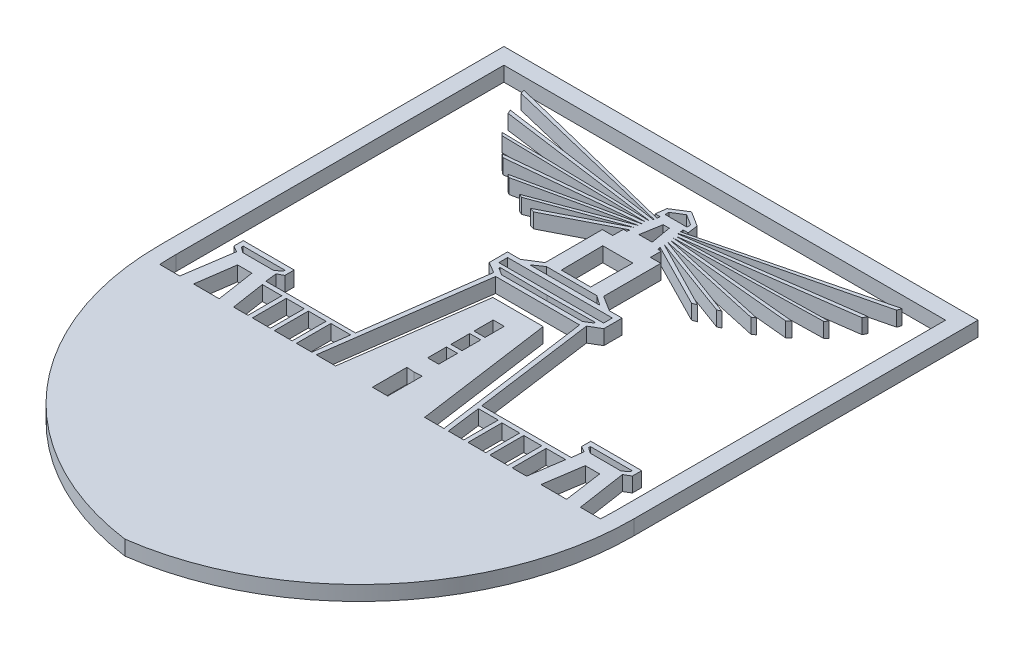
SolidWorks part; units mm, degrees
material "Acrylic (Medium-high impact)"
ref_plane "Front Plane" through (0, 0, 0) normal (0, 0, 1) x (1, 0, 0)
ref_plane "Top Plane" through (0, 0, 0) normal (0, 1, 0) x (1, 0, 0)
ref_plane "Right Plane" through (0, 0, 0) normal (1, 0, 0) x (0, 0, -1)
sketch "Sketch1" plane through (0, 0, 0) normal (0, 1, 0) x (1, 0, 0)
  line L0 (0, 0) -> (5, 0) construction
  line L1 (338.282, 207.287) -> (338.282, 90.5991)
  line L2 (338.282, 207.287) -> (418.6487, 207.287)
  line L3 (418.6487, 207.287) -> (418.6487, 205.1656) construction
  line L4 (343.782, 201.787) -> (418.6487, 201.787)
  line L5 (343.782, 201.787) -> (343.782, 90.5991)
  line L6 (343.9648, 84.9427) -> (350.7389, 84.9427)
  line L7 (350.7389, 84.9427) -> (353.2346, 101.6759)
  line L8 (353.2346, 101.6759) -> (351.1115, 102.9309)
  line L9 (351.1115, 102.9309) -> (351.1115, 106.1012)
  line L10 (351.1115, 106.1012) -> (368.3755, 106.1012)
  line L11 (368.3755, 106.1012) -> (368.3755, 102.9309)
  line L12 (368.3755, 102.9309) -> (366.4294, 101.8951)
  line L13 (366.4294, 101.8951) -> (366.8689, 98.0028)
  line L14 (366.8689, 98.0028) -> (397.265, 98.0028)
  line L15 (397.265, 98.0028) -> (402.9132, 139.1779)
  line L16 (402.9132, 139.1779) -> (399.2205, 141.3608)
  line L17 (399.2205, 141.3608) -> (399.2205, 147.5615)
  line L18 (399.2205, 147.5615) -> (403.5436, 147.5615)
  line L19 (403.5436, 147.5615) -> (408.7386, 150.824)
  line L20 (408.7386, 150.824) -> (408.7386, 170.1989)
  line L21 (408.7386, 170.1989) -> (412.2526, 170.1989)
  line L22 (412.2526, 170.1989) -> (412.2526, 173.8284)
  line L23 (412.2526, 173.8284) -> (413.3988, 173.8284)
  line L24 (413.3988, 173.8284) -> (414.7661, 183.7962)
  line L25 (414.7661, 183.7962) -> (413.0651, 183.7962)
  line L26 (413.0651, 183.7962) -> (413.5499, 187.3303)
  line L27 (413.5499, 187.3303) -> (418.6487, 190.5324)
  line L28 (350.7389, 84.9427) -> (486.5585, 84.9427)
  line L29 (355.4177, 84.9427) -> (357.2644, 98.0028)
  line L30 (357.2644, 98.0028) -> (362.135, 98.0028)
  line L31 (362.135, 98.0028) -> (364.0997, 84.9427)
  line L32 (357.2765, 84.9427) -> (358.6439, 96.4394)
  line L33 (358.6439, 96.4394) -> (360.8995, 96.4394)
  line L34 (360.8995, 96.4394) -> (362.5434, 84.9427)
  line L35 (352.719, 104.4668) -> (366.8689, 104.4668)
  line L36 (366.8689, 104.4668) -> (366.8689, 103.849)
  line L37 (366.8689, 103.849) -> (364.951, 102.4899)
  line L38 (364.951, 102.4899) -> (354.5312, 102.4899)
  line L39 (354.5312, 102.4899) -> (352.719, 103.849)
  line L40 (352.719, 103.849) -> (352.719, 104.4668)
  line L41 (403.5578, 84.9427) -> (410.1037, 131.7143)
  line L42 (410.1037, 131.7143) -> (427.1937, 131.7143)
  line L43 (400.8893, 142.966) -> (436.408, 142.966)
  line L44 (418.6487, 142.966) -> (418.6487, 145.9394)
  line L45 (436.408, 145.9394) -> (400.8893, 145.9394)
  line L46 (400.8893, 145.9394) -> (400.8893, 142.966)
  line L47 (402.5078, 141.7616) -> (402.5078, 141.3608)
  line L48 (402.5078, 141.3608) -> (404.9542, 139.842)
  line L49 (404.9542, 139.842) -> (432.3431, 139.842)
  line L50 (418.6487, 139.842) -> (418.6487, 141.5616)
  line L51 (418.6487, 141.5616) -> (402.5078, 141.7616)
  line L52 (406.8086, 147.5615) -> (410.1037, 149.8728)
  line L53 (410.1037, 149.8728) -> (427.1937, 149.8728)
  line L54 (406.8086, 147.5615) -> (430.4887, 147.5615)
  line L55 (414.6308, 182.8096) -> (354.5312, 197.8348)
  line L56 (354.5312, 197.8348) -> (354.9929, 196.4245)
  line L57 (354.9929, 196.4245) -> (414.5137, 181.9557)
  line L58 (414.4848, 181.745) -> (358.0193, 189.685)
  line L59 (358.0193, 189.685) -> (358.6488, 188.3516)
  line L60 (358.6488, 188.3516) -> (414.343, 180.7117)
  line L61 (414.343, 180.7117) -> (363.2021, 181.745)
  line L62 (363.2021, 181.745) -> (364.1351, 180.7734)
  line L63 (364.1351, 180.7734) -> (414.2127, 179.7616)
  line L64 (422.3648, 185.2721) -> (414.9326, 185.2721)
  line L65 (414.9326, 185.2721) -> (414.9326, 186.5349)
  line L66 (414.9326, 186.5349) -> (418.6487, 188.849)
  line L67 (373.8379, 84.9427) -> (373.8379, 96.4394)
  line L68 (373.8379, 96.4394) -> (367.2313, 96.4394)
  line L69 (367.2313, 96.4394) -> (368.987, 84.9427)
  line L70 (375.3556, 96.4394) -> (375.3556, 84.9427)
  line L71 (375.3556, 84.9427) -> (381.4265, 84.9427)
  line L72 (381.4265, 84.9427) -> (381.4265, 96.4394)
  line L73 (381.4265, 96.4394) -> (375.3556, 96.4394)
  line L74 (382.8287, 84.9427) -> (382.8287, 96.4463)
  line L75 (382.8287, 96.4463) -> (388.8336, 96.4463)
  line L76 (388.8336, 96.4463) -> (388.8336, 84.9427)
  line L77 (390.2871, 96.6243) -> (390.2871, 84.9427)
  line L78 (390.2871, 96.6243) -> (396.9907, 96.6243)
  line L79 (396.9907, 96.6243) -> (395.491, 84.9427)
  line L80 (397.0048, 84.9427) -> (404.4186, 138.3529)
  line L81 (404.4186, 138.3529) -> (432.8787, 138.3529)
  line L82 (419.6894, 181.9557) -> (417.6079, 181.9557)
  line L83 (417.6079, 181.9557) -> (416.4096, 174.941)
  line L84 (416.4096, 174.941) -> (420.8877, 174.941)
  line L85 (418.8634, 180.9228) -> (418.434, 180.9228)
  line L86 (418.434, 180.9228) -> (417.8251, 176.113)
  line L87 (417.8251, 176.113) -> (419.4722, 176.113)
  line L88 (412.2526, 151.358) -> (412.2526, 167.1023)
  line L89 (412.2526, 167.1023) -> (425.0447, 167.1023)
  line L90 (423.7475, 165.5348) -> (413.5499, 165.5348)
  line L91 (413.5499, 165.5348) -> (413.6837, 151.358)
  line L92 (413.6837, 151.358) -> (423.6137, 151.358)
  line L93 (418.434, 130.1574) -> (411.6143, 130.1574)
  line L94 (411.6143, 130.1574) -> (404.9692, 84.9427)
  line L95 (414.2127, 179.7616) -> (369.5177, 175.4706)
  line L96 (369.5177, 175.4706) -> (370.7239, 174.4757)
  line L97 (370.7239, 174.4757) -> (413.9507, 178.6258)
  line L98 (413.9507, 178.6258) -> (376.4718, 170.4145)
  line L99 (376.4718, 170.4145) -> (377.6526, 169.6582)
  line L100 (377.6526, 169.6582) -> (413.9166, 177.6033)
  line L101 (413.9166, 177.6033) -> (384.3715, 166.5403)
  line L102 (384.3715, 166.5403) -> (385.5687, 165.9954)
  line L103 (385.5687, 165.9954) -> (413.7408, 176.3215)
  line L104 (413.7408, 176.3215) -> (390.2871, 164.2335)
  line L105 (390.2871, 164.2335) -> (391.8652, 163.7288)
  line L106 (391.8652, 163.7288) -> (413.529, 174.7775)
  line L107 (414.4848, 85.1259) -> (414.4848, 98.0028)
  line L108 (414.4848, 98.0028) -> (422.8126, 98.0028)
  line L109 (416.0563, 84.9427) -> (416.0563, 96.6243)
  line L110 (416.0563, 96.6243) -> (418.6487, 96.4463)
  line L111 (420.5185, 102.9309) -> (416.7789, 102.9309)
  line L112 (416.7789, 102.9309) -> (416.7789, 109.3146)
  line L113 (416.7789, 109.3146) -> (420.5185, 109.3146)
  line L114 (419.3869, 108.1591) -> (417.9105, 108.1591)
  line L115 (417.9105, 108.1591) -> (417.9105, 103.9613)
  line L116 (417.9105, 103.9613) -> (419.3869, 103.9613)
  line L117 (420.5185, 125.164) -> (416.7789, 125.164)
  line L118 (416.7789, 125.164) -> (416.7789, 118.6557)
  line L119 (416.7789, 118.6557) -> (420.5185, 118.6557)
  line L120 (419.3869, 119.9212) -> (417.9105, 119.9212)
  line L121 (417.9105, 119.9212) -> (417.9105, 124.0341)
  line L122 (417.9105, 124.0341) -> (419.3869, 124.0341)
  line L123 (395.2823, 95.3731) -> (391.4774, 95.3731)
  line L124 (391.4774, 95.3731) -> (391.4774, 91.7404)
  line L125 (391.4774, 91.7404) -> (395.2823, 91.7404)
  line L126 (395.2823, 91.7404) -> (395.2823, 95.3731)
  line L127 (392.5991, 92.7292) -> (392.5991, 94.2466)
  line L128 (392.5991, 94.2466) -> (394.0882, 94.2466)
  line L129 (394.0882, 94.2466) -> (394.0882, 92.7434)
  line L130 (394.0882, 92.7434) -> (392.5991, 92.7292)
  line L131 (384.0554, 91.7404) -> (384.0554, 95.3731)
  line L132 (384.0554, 95.3731) -> (387.7088, 95.3731)
  line L133 (387.7088, 95.3731) -> (387.7088, 91.7404)
  line L134 (387.7088, 91.7404) -> (384.0554, 91.7404)
  line L135 (385.1139, 94.2466) -> (385.1139, 92.7292)
  line L136 (385.1139, 92.7292) -> (386.6701, 92.7292)
  line L137 (386.6701, 92.7292) -> (386.6701, 94.2466)
  line L138 (386.6701, 94.2466) -> (385.1139, 94.2466)
  line L139 (420.5185, 117.2088) -> (416.7789, 117.2088)
  line L140 (416.7789, 117.2088) -> (416.7789, 110.8551)
  line L141 (416.7789, 110.8551) -> (420.5185, 110.8551)
  line L142 (418.6487, 110.8551) -> (418.6487, 112.0248)
  line L143 (419.3869, 112.0248) -> (417.9105, 112.0248)
  line L144 (417.9105, 112.0248) -> (417.9105, 116.039)
  line L145 (417.9105, 116.039) -> (419.3869, 116.039)
  line L146 (376.4718, 91.6125) -> (380.3389, 91.6125)
  line L147 (380.3389, 91.6125) -> (380.3389, 95.3731)
  line L148 (380.3389, 95.3731) -> (376.4718, 95.3731)
  line L149 (376.4718, 95.3731) -> (376.4718, 91.6125)
  line L150 (377.6526, 94.2466) -> (377.6526, 92.7292)
  line L151 (377.6526, 92.7292) -> (379.2994, 92.7292)
  line L152 (379.2994, 92.7292) -> (379.2994, 94.2466)
  line L153 (379.2994, 94.2466) -> (377.6526, 94.2466)
  line L154 (379.2994, 94.2466) -> (379.0544, 93.6718)
  line L155 (368.987, 91.6125) -> (368.987, 95.3731)
  line L156 (368.987, 95.3731) -> (372.7392, 95.3731)
  line L157 (372.7392, 95.3731) -> (372.7392, 91.6125)
  line L158 (372.7392, 91.6125) -> (368.987, 91.6125)
  line L159 (370.043, 92.7292) -> (371.6081, 92.7292)
  line L160 (371.6081, 92.7292) -> (371.6081, 94.2484)
  line L161 (371.6081, 94.2484) -> (370.043, 94.2484)
  line L162 (370.043, 94.2484) -> (370.043, 92.7292)
  line L163 (467.2543, 94.2484) -> (467.2543, 92.7292)
  line L164 (465.6893, 94.2484) -> (467.2543, 94.2484)
  line L165 (465.6893, 92.7292) -> (465.6893, 94.2484)
  line L166 (467.2543, 92.7292) -> (465.6893, 92.7292)
  line L167 (464.5581, 91.6125) -> (468.3103, 91.6125)
  line L168 (464.5581, 95.3731) -> (464.5581, 91.6125)
  line L169 (468.3103, 95.3731) -> (464.5581, 95.3731)
  line L170 (468.3103, 91.6125) -> (468.3103, 95.3731)
  line L171 (457.9979, 94.2466) -> (458.243, 93.6718)
  line L172 (457.9979, 94.2466) -> (459.6448, 94.2466)
  line L173 (457.9979, 92.7292) -> (457.9979, 94.2466)
  line L174 (459.6448, 92.7292) -> (457.9979, 92.7292)
  line L175 (459.6448, 94.2466) -> (459.6448, 92.7292)
  line L176 (460.8255, 95.3731) -> (460.8255, 91.6125)
  line L177 (456.9585, 95.3731) -> (460.8255, 95.3731)
  line L178 (456.9585, 91.6125) -> (456.9585, 95.3731)
  line L179 (460.8255, 91.6125) -> (456.9585, 91.6125)
  line L180 (419.3869, 112.0248) -> (419.3869, 116.039)
  line L181 (420.5185, 117.2088) -> (420.5185, 110.8551)
  line L182 (450.6273, 94.2466) -> (452.1835, 94.2466)
  line L183 (450.6273, 92.7292) -> (450.6273, 94.2466)
  line L184 (452.1835, 92.7292) -> (450.6273, 92.7292)
  line L185 (452.1835, 94.2466) -> (452.1835, 92.7292)
  line L186 (449.5886, 91.7404) -> (453.242, 91.7404)
  line L187 (449.5886, 95.3731) -> (449.5886, 91.7404)
  line L188 (453.242, 95.3731) -> (449.5886, 95.3731)
  line L189 (453.242, 91.7404) -> (453.242, 95.3731)
  line L190 (443.2092, 92.7434) -> (444.6982, 92.7292)
  line L191 (443.2092, 94.2466) -> (443.2092, 92.7434)
  line L192 (444.6982, 94.2466) -> (443.2092, 94.2466)
  line L193 (444.6982, 92.7292) -> (444.6982, 94.2466)
  line L194 (442.0151, 91.7404) -> (442.0151, 95.3731)
  line L195 (445.82, 91.7404) -> (442.0151, 91.7404)
  line L196 (445.82, 95.3731) -> (445.82, 91.7404)
  line L197 (442.0151, 95.3731) -> (445.82, 95.3731)
  line L198 (419.3869, 119.9212) -> (419.3869, 124.0341)
  line L199 (420.5185, 125.164) -> (420.5185, 118.6557)
  line L200 (419.3869, 108.1591) -> (419.3869, 103.9613)
  line L201 (420.5185, 102.9309) -> (420.5185, 109.3146)
  line L202 (421.241, 96.6243) -> (418.6487, 96.4463)
  line L203 (421.241, 84.9427) -> (421.241, 96.6243)
  line L204 (422.8126, 85.1259) -> (422.8126, 98.0028)
  line L205 (445.4321, 163.7288) -> (423.7684, 174.7775)
  line L206 (447.0103, 164.2335) -> (445.4321, 163.7288)
  line L207 (423.5566, 176.3215) -> (447.0103, 164.2335)
  line L208 (451.7287, 165.9954) -> (423.5566, 176.3215)
  line L209 (452.9258, 166.5403) -> (451.7287, 165.9954)
  line L210 (423.3807, 177.6033) -> (452.9258, 166.5403)
  line L211 (459.6448, 169.6582) -> (423.3807, 177.6033)
  line L212 (460.8255, 170.4145) -> (459.6448, 169.6582)
  line L213 (423.3467, 178.6258) -> (460.8255, 170.4145)
  line L214 (466.5735, 174.4757) -> (423.3467, 178.6258)
  line L215 (467.7796, 175.4706) -> (466.5735, 174.4757)
  line L216 (423.0847, 179.7616) -> (467.7796, 175.4706)
  line L217 (425.683, 130.1574) -> (432.3282, 84.9427)
  line L218 (418.8634, 130.1574) -> (425.683, 130.1574)
  line L219 (423.7475, 165.5348) -> (423.6137, 151.358)
  line L220 (425.0447, 151.358) -> (425.0447, 167.1023)
  line L221 (418.8634, 180.9228) -> (419.4722, 176.113)
  line L222 (419.6894, 181.9557) -> (420.8877, 174.941)
  line L223 (440.2925, 84.9427) -> (432.8787, 138.3529)
  line L224 (440.3066, 96.6243) -> (441.8064, 84.9427)
  line L225 (447.0103, 96.6243) -> (440.3066, 96.6243)
  line L226 (447.0103, 96.6243) -> (447.0103, 84.9427)
  line L227 (448.4637, 96.4463) -> (448.4637, 84.9427)
  line L228 (454.4686, 96.4463) -> (448.4637, 96.4463)
  line L229 (454.4686, 84.9427) -> (454.4686, 96.4463)
  line L230 (455.8709, 96.4394) -> (461.9418, 96.4394)
  line L231 (455.8709, 84.9427) -> (455.8709, 96.4394)
  line L232 (461.9418, 84.9427) -> (455.8709, 84.9427)
  line L233 (461.9418, 96.4394) -> (461.9418, 84.9427)
  line L234 (470.066, 96.4394) -> (468.3103, 84.9427)
  line L235 (463.4595, 96.4394) -> (470.066, 96.4394)
  line L236 (463.4595, 84.9427) -> (463.4595, 96.4394)
  line L237 (422.3648, 186.5349) -> (418.6487, 188.849)
  line L238 (422.3648, 185.2721) -> (422.3648, 186.5349)
  line L239 (473.1622, 180.7734) -> (423.0847, 179.7616)
  line L240 (474.0953, 181.745) -> (473.1622, 180.7734)
  line L241 (422.9543, 180.7117) -> (474.0953, 181.745)
  line L242 (478.6486, 188.3516) -> (422.9543, 180.7117)
  line L243 (479.278, 189.685) -> (478.6486, 188.3516)
  line L244 (422.8126, 181.745) -> (479.278, 189.685)
  line L245 (482.3045, 196.4245) -> (422.7837, 181.9557)
  line L246 (482.7662, 197.8348) -> (482.3045, 196.4245)
  line L247 (422.6665, 182.8096) -> (482.7662, 197.8348)
  line L248 (430.4887, 147.5615) -> (427.1937, 149.8728)
  line L249 (418.6487, 141.5616) -> (434.7896, 141.7616)
  line L250 (434.7896, 141.3608) -> (432.3431, 139.842)
  line L251 (434.7896, 141.7616) -> (434.7896, 141.3608)
  line L252 (436.408, 145.9394) -> (436.408, 142.966)
  line L253 (433.7396, 84.9427) -> (427.1937, 131.7143)
  line L254 (484.5783, 103.849) -> (484.5783, 104.4668)
  line L255 (482.7662, 102.4899) -> (484.5783, 103.849)
  line L256 (472.3463, 102.4899) -> (482.7662, 102.4899)
  line L257 (470.4285, 103.849) -> (472.3463, 102.4899)
  line L258 (470.4285, 104.4668) -> (470.4285, 103.849)
  line L259 (484.5783, 104.4668) -> (470.4285, 104.4668)
  line L260 (476.3979, 96.4394) -> (474.7539, 84.9427)
  line L261 (478.6534, 96.4394) -> (476.3979, 96.4394)
  line L262 (480.0208, 84.9427) -> (478.6534, 96.4394)
  line L263 (475.1623, 98.0028) -> (473.1977, 84.9427)
  line L264 (480.0329, 98.0028) -> (475.1623, 98.0028)
  line L265 (481.8797, 84.9427) -> (480.0329, 98.0028)
  line L266 (423.7475, 187.3303) -> (418.6487, 190.5324)
  line L267 (424.2323, 183.7962) -> (423.7475, 187.3303)
  line L268 (422.5312, 183.7962) -> (424.2323, 183.7962)
  line L269 (423.8986, 173.8284) -> (422.5312, 183.7962)
  line L270 (425.0447, 173.8284) -> (423.8986, 173.8284)
  line L271 (425.0447, 170.1989) -> (425.0447, 173.8284)
  line L272 (428.5588, 170.1989) -> (425.0447, 170.1989)
  line L273 (428.5588, 150.824) -> (428.5588, 170.1989)
  line L274 (433.7538, 147.5615) -> (428.5588, 150.824)
  line L275 (438.0769, 147.5615) -> (433.7538, 147.5615)
  line L276 (438.0769, 141.3608) -> (438.0769, 147.5615)
  line L277 (434.3841, 139.1779) -> (438.0769, 141.3608)
  line L278 (440.0324, 98.0028) -> (434.3841, 139.1779)
  line L279 (470.4285, 98.0028) -> (440.0324, 98.0028)
  line L280 (470.8679, 101.8951) -> (470.4285, 98.0028)
  line L281 (468.9218, 102.9309) -> (470.8679, 101.8951)
  line L282 (468.9218, 106.1012) -> (468.9218, 102.9309)
  line L283 (486.1858, 106.1012) -> (468.9218, 106.1012)
  line L284 (486.1858, 102.9309) -> (486.1858, 106.1012)
  line L285 (484.0628, 101.6759) -> (486.1858, 102.9309)
  line L286 (486.5585, 84.9427) -> (484.0628, 101.6759)
  line L287 (493.3325, 84.9427) -> (486.5585, 84.9427)
  line L288 (493.5154, 201.787) -> (493.5154, 90.5991)
  line L289 (493.5154, 201.787) -> (418.6487, 201.787)
  line L290 (499.0154, 207.287) -> (418.6487, 207.287)
  line L291 (499.0154, 207.287) -> (499.0154, 90.5991)
  arc A0 (338.282, 90.5991) -> (418.6487, -1.6094) centre (431.3629, 90.5991) ccw
  arc A1 (343.782, 90.5991) -> (418.6487, 3.946) centre (431.3629, 90.5991) ccw
  arc A3 (493.5154, 90.5991) -> (418.6487, 3.946) centre (405.9345, 90.5991) cw
  arc A4 (499.0154, 90.5991) -> (418.6487, -1.6094) centre (405.9345, 90.5991) cw
  point P217 (418.6487, 116.039)
  point P220 (418.6487, 117.2088)
  point P237 (418.6487, 124.0341)
  point P238 (418.6487, 119.9212)
  point P239 (418.6487, 118.6557)
  point P240 (418.6487, 125.164)
  point P241 (418.6487, 103.9613)
  point P242 (418.6487, 108.1591)
  point P243 (418.6487, 109.3146)
  point P244 (418.6487, 102.9309)
  point P247 (418.6487, 98.0028)
  point P265 (418.6487, 151.358)
  point P266 (418.6487, 165.5348)
  point P267 (418.6487, 167.1023)
  point P269 (418.6487, 176.113)
  point P270 (418.6487, 180.9228)
  point P271 (418.6487, 174.941)
  point P272 (418.6487, 181.9557)
  point P273 (418.6487, 138.3529)
  point P292 (418.6487, 185.2721)
  point P303 (418.6487, 147.5615)
  point P304 (418.6487, 149.8728)
  point P310 (418.6487, 131.7143)
  point P326 (418.6487, 84.9427)
  dimension "D1" = 5
  dimension "D3" = 2.1214
  dimension "D2" = 208.8964
extrude "Boss-Extrude1" add sketch "Sketch1" along normal blind 5 contours A4 L291 L290 L2 L1 A0 L288 A3 A1 L5 L4 L289 | L28 L286 L285 L284 L283 L282 L281 L280 L279 L278 L277 L276 L275 L274 L273 L272 L271 L270 L269 L268 L267 L266 L27 L26 L25 L24 L23 L22 region at (378.4653, 0, -204.6512) region at (353.6883, 0, -93.0556)
sketch "Sketch2" plane through (0, 0, 0) normal (0, 1, 0) x (1, 0, 0)
  line L0 (493.3325, 84.9427) -> (486.5585, 84.9427) construction
  line L1 (343.9648, 84.9427) -> (350.7389, 84.9427) construction
  line L2 (350.7389, 84.9427) -> (486.5585, 84.9427) construction
  line L3 (422.8126, 181.745) -> (479.278, 189.685) construction
  line L4 (479.278, 189.685) -> (478.6486, 188.3516) construction
  line L5 (478.6486, 188.3516) -> (422.9543, 180.7117) construction
  line L6 (422.9543, 180.7117) -> (474.0953, 181.745) construction
  line L7 (474.0953, 181.745) -> (473.1622, 180.7734) construction
  line L8 (473.1622, 180.7734) -> (423.0847, 179.7616) construction
  line L9 (423.0847, 179.7616) -> (467.7796, 175.4706) construction
  line L10 (467.7796, 175.4706) -> (466.5735, 174.4757) construction
  line L11 (466.5735, 174.4757) -> (423.3467, 178.6258) construction
  line L12 (423.3467, 178.6258) -> (460.8255, 170.4145) construction
  line L13 (460.8255, 170.4145) -> (459.6448, 169.6582) construction
  line L14 (459.6448, 169.6582) -> (423.3807, 177.6033) construction
  line L15 (423.3807, 177.6033) -> (452.9258, 166.5403) construction
  line L16 (452.9258, 166.5403) -> (451.7287, 165.9954) construction
  line L17 (451.7287, 165.9954) -> (423.5566, 176.3215) construction
  line L18 (423.5566, 176.3215) -> (447.0103, 164.2335) construction
  line L19 (447.0103, 164.2335) -> (445.4321, 163.7288) construction
  line L20 (445.4321, 163.7288) -> (423.7684, 174.7775) construction
  line L21 (482.3045, 196.4245) -> (422.7837, 181.9557) construction
  line L22 (422.6665, 182.8096) -> (482.7662, 197.8348) construction
  line L23 (482.7662, 197.8348) -> (482.3045, 196.4245) construction
  line L24 (414.6308, 182.8096) -> (354.5312, 197.8348) construction
  line L25 (354.5312, 197.8348) -> (354.9929, 196.4245) construction
  line L26 (354.9929, 196.4245) -> (414.5137, 181.9557) construction
  line L27 (414.4848, 181.745) -> (358.0193, 189.685) construction
  line L28 (358.0193, 189.685) -> (358.6488, 188.3516) construction
  line L29 (358.6488, 188.3516) -> (414.343, 180.7117) construction
  line L30 (414.343, 180.7117) -> (363.2021, 181.745) construction
  line L31 (363.2021, 181.745) -> (364.1351, 180.7734) construction
  line L32 (364.1351, 180.7734) -> (414.2127, 179.7616) construction
  line L33 (414.2127, 179.7616) -> (369.5177, 175.4706) construction
  line L34 (369.5177, 175.4706) -> (370.7239, 174.4757) construction
  line L35 (370.7239, 174.4757) -> (413.9507, 178.6258) construction
  line L36 (413.9507, 178.6258) -> (376.4718, 170.4145) construction
  line L37 (376.4718, 170.4145) -> (377.6526, 169.6582) construction
  line L38 (377.6526, 169.6582) -> (413.9166, 177.6033) construction
  line L39 (413.9166, 177.6033) -> (384.3715, 166.5403) construction
  line L40 (384.3715, 166.5403) -> (385.5687, 165.9954) construction
  line L41 (385.5687, 165.9954) -> (413.7408, 176.3215) construction
  line L42 (413.7408, 176.3215) -> (390.2871, 164.2335) construction
  line L43 (390.2871, 164.2335) -> (391.8652, 163.7288) construction
  line L44 (391.8652, 163.7288) -> (413.529, 174.7775) construction
  line L45 (413.5499, 187.3303) -> (418.6487, 190.5324) construction
  line L46 (350.7389, 84.9427) -> (353.2346, 101.6759) construction
  line L47 (353.2346, 101.6759) -> (351.1115, 102.9309) construction
  line L48 (351.1115, 102.9309) -> (351.1115, 106.1012) construction
  line L49 (351.1115, 106.1012) -> (368.3755, 106.1012) construction
  line L50 (368.3755, 106.1012) -> (368.3755, 102.9309) construction
  line L51 (368.3755, 102.9309) -> (366.4294, 101.8951) construction
  line L52 (366.4294, 101.8951) -> (366.8689, 98.0028) construction
  line L53 (366.8689, 98.0028) -> (397.265, 98.0028) construction
  line L54 (397.265, 98.0028) -> (402.9132, 139.1779) construction
  line L55 (402.9132, 139.1779) -> (399.2205, 141.3608) construction
  line L56 (399.2205, 141.3608) -> (399.2205, 147.5615) construction
  line L57 (399.2205, 147.5615) -> (403.5436, 147.5615) construction
  line L58 (403.5436, 147.5615) -> (408.7386, 150.824) construction
  line L59 (408.7386, 150.824) -> (408.7386, 170.1989) construction
  line L60 (408.7386, 170.1989) -> (412.2526, 170.1989) construction
  line L61 (412.2526, 170.1989) -> (412.2526, 173.8284) construction
  line L62 (412.2526, 173.8284) -> (413.3988, 173.8284) construction
  line L63 (413.3988, 173.8284) -> (414.7661, 183.7962) construction
  line L64 (414.7661, 183.7962) -> (413.0651, 183.7962) construction
  line L65 (413.0651, 183.7962) -> (413.5499, 187.3303) construction
  line L66 (423.7475, 187.3303) -> (418.6487, 190.5324) construction
  line L67 (424.2323, 183.7962) -> (423.7475, 187.3303) construction
  line L68 (422.5312, 183.7962) -> (424.2323, 183.7962) construction
  line L69 (423.8986, 173.8284) -> (422.5312, 183.7962) construction
  line L70 (425.0447, 173.8284) -> (423.8986, 173.8284) construction
  line L71 (425.0447, 170.1989) -> (425.0447, 173.8284) construction
  line L72 (428.5588, 170.1989) -> (425.0447, 170.1989) construction
  line L73 (428.5588, 150.824) -> (428.5588, 170.1989) construction
  line L74 (433.7538, 147.5615) -> (428.5588, 150.824) construction
  line L75 (438.0769, 147.5615) -> (433.7538, 147.5615) construction
  line L76 (438.0769, 141.3608) -> (438.0769, 147.5615) construction
  line L77 (434.3841, 139.1779) -> (438.0769, 141.3608) construction
  line L78 (440.0324, 98.0028) -> (434.3841, 139.1779) construction
  line L79 (470.4285, 98.0028) -> (440.0324, 98.0028) construction
  line L80 (470.8679, 101.8951) -> (470.4285, 98.0028) construction
  line L81 (468.9218, 102.9309) -> (470.8679, 101.8951) construction
  line L82 (468.9218, 106.1012) -> (468.9218, 102.9309) construction
  line L83 (486.1858, 106.1012) -> (468.9218, 106.1012) construction
  line L84 (486.1858, 102.9309) -> (486.1858, 106.1012) construction
  line L85 (484.0628, 101.6759) -> (486.1858, 102.9309) construction
  line L86 (486.5585, 84.9427) -> (484.0628, 101.6759) construction
  line L87 (481.8797, 84.9427) -> (486.5585, 84.9427)
  line L88 (486.5585, 84.9427) -> (484.0628, 101.6759)
  line L89 (484.0628, 101.6759) -> (486.1858, 102.9309)
  line L90 (486.1858, 102.9309) -> (486.1858, 106.1012)
  line L91 (486.1858, 106.1012) -> (468.9218, 106.1012)
  line L92 (468.9218, 106.1012) -> (468.9218, 102.9309)
  line L93 (468.9218, 102.9309) -> (470.8679, 101.8951)
  line L94 (470.8679, 101.8951) -> (470.4285, 98.0028)
  line L95 (470.4285, 98.0028) -> (440.0324, 98.0028)
  line L96 (440.0324, 98.0028) -> (434.3841, 139.1779)
  line L97 (434.3841, 139.1779) -> (438.0769, 141.3608)
  line L98 (438.0769, 141.3608) -> (438.0769, 147.5615)
  line L99 (438.0769, 147.5615) -> (433.7538, 147.5615)
  line L100 (433.7538, 147.5615) -> (428.5588, 150.824)
  line L101 (428.5588, 150.824) -> (428.5588, 170.1989)
  line L102 (428.5588, 170.1989) -> (425.0447, 170.1989)
  line L103 (425.0447, 170.1989) -> (425.0447, 173.8284)
  line L104 (425.0447, 173.8284) -> (423.8986, 173.8284)
  line L105 (423.8986, 173.8284) -> (422.5312, 183.7962)
  line L106 (422.5312, 183.7962) -> (424.2323, 183.7962)
  line L107 (424.2323, 183.7962) -> (423.7475, 187.3303)
  line L108 (423.7475, 187.3303) -> (418.6487, 190.5324)
  line L109 (418.6487, 190.5324) -> (413.5499, 187.3303)
  line L110 (413.5499, 187.3303) -> (413.0651, 183.7962)
  line L111 (413.0651, 183.7962) -> (414.7661, 183.7962)
  line L112 (414.7661, 183.7962) -> (413.3988, 173.8284)
  line L113 (413.3988, 173.8284) -> (412.2526, 173.8284)
  line L114 (412.2526, 173.8284) -> (412.2526, 170.1989)
  line L115 (412.2526, 170.1989) -> (408.7386, 170.1989)
  line L116 (408.7386, 170.1989) -> (408.7386, 150.824)
  line L117 (408.7386, 150.824) -> (403.5436, 147.5615)
  line L118 (403.5436, 147.5615) -> (399.2205, 147.5615)
  line L119 (399.2205, 147.5615) -> (399.2205, 141.3608)
  line L120 (399.2205, 141.3608) -> (402.9132, 139.1779)
  line L121 (402.9132, 139.1779) -> (397.265, 98.0028)
  line L122 (397.265, 98.0028) -> (366.8689, 98.0028)
  line L123 (366.8689, 98.0028) -> (366.4294, 101.8951)
  line L124 (366.4294, 101.8951) -> (368.3755, 102.9309)
  line L125 (368.3755, 102.9309) -> (368.3755, 106.1012)
  line L126 (368.3755, 106.1012) -> (351.1115, 106.1012)
  line L127 (351.1115, 106.1012) -> (351.1115, 102.9309)
  line L128 (351.1115, 102.9309) -> (353.2346, 101.6759)
  line L129 (353.2346, 101.6759) -> (350.7389, 84.9427)
  line L130 (350.7389, 84.9427) -> (355.4177, 84.9427)
  line L131 (355.4177, 84.9427) -> (357.2644, 98.0028)
  line L132 (357.2644, 98.0028) -> (362.135, 98.0028)
  line L133 (362.135, 98.0028) -> (364.0997, 84.9427)
  line L134 (364.0997, 84.9427) -> (368.987, 84.9427)
  line L135 (368.987, 84.9427) -> (367.2313, 96.4394)
  line L136 (367.2313, 96.4394) -> (373.8379, 96.4394)
  line L137 (373.8379, 96.4394) -> (373.8379, 84.9427)
  line L138 (373.8379, 84.9427) -> (375.3556, 84.9427)
  line L139 (375.3556, 84.9427) -> (375.3556, 96.4394)
  line L140 (375.3556, 96.4394) -> (381.4265, 96.4394)
  line L141 (381.4265, 96.4394) -> (381.4265, 84.9427)
  line L142 (381.4265, 84.9427) -> (382.8287, 84.9427)
  line L143 (382.8287, 84.9427) -> (382.8287, 96.4463)
  line L144 (382.8287, 96.4463) -> (388.8336, 96.4463)
  line L145 (388.8336, 96.4463) -> (388.8336, 84.9427)
  line L146 (388.8336, 84.9427) -> (390.2871, 84.9427)
  line L147 (390.2871, 84.9427) -> (390.2871, 96.6243)
  line L148 (390.2871, 96.6243) -> (396.9907, 96.6243)
  line L149 (396.9907, 96.6243) -> (395.491, 84.9427)
  line L150 (395.491, 84.9427) -> (397.0048, 84.9427)
  line L151 (397.0048, 84.9427) -> (404.4186, 138.3529)
  line L152 (404.4186, 138.3529) -> (432.8787, 138.3529)
  line L153 (432.8787, 138.3529) -> (440.2925, 84.9427)
  line L154 (440.2925, 84.9427) -> (441.8064, 84.9427)
  line L155 (441.8064, 84.9427) -> (440.3066, 96.6243)
  line L156 (440.3066, 96.6243) -> (447.0103, 96.6243)
  line L157 (447.0103, 96.6243) -> (447.0103, 84.9427)
  line L158 (447.0103, 84.9427) -> (448.4637, 84.9427)
  line L159 (448.4637, 84.9427) -> (448.4637, 96.4463)
  line L160 (448.4637, 96.4463) -> (454.4686, 96.4463)
  line L161 (454.4686, 96.4463) -> (454.4686, 84.9427)
  line L162 (454.4686, 84.9427) -> (455.8709, 84.9427)
  line L163 (455.8709, 84.9427) -> (455.8709, 96.4394)
  line L164 (455.8709, 96.4394) -> (461.9418, 96.4394)
  line L165 (461.9418, 96.4394) -> (461.9418, 84.9427)
  line L166 (461.9418, 84.9427) -> (463.4595, 84.9427)
  line L167 (463.4595, 84.9427) -> (463.4595, 96.4394)
  line L168 (463.4595, 96.4394) -> (470.066, 96.4394)
  line L169 (470.066, 96.4394) -> (468.3103, 84.9427)
  line L170 (468.3103, 84.9427) -> (473.1977, 84.9427)
  line L171 (473.1977, 84.9427) -> (475.1623, 98.0028)
  line L172 (475.1623, 98.0028) -> (480.0329, 98.0028)
  line L173 (480.0329, 98.0028) -> (481.8797, 84.9427)
  line L174 (481.8797, 84.9427) -> (486.5585, 84.9427)
  line L175 (486.5585, 84.9427) -> (484.0628, 101.6759)
  line L176 (484.0628, 101.6759) -> (486.1858, 102.9309)
  line L177 (486.1858, 102.9309) -> (486.1858, 106.1012)
  line L178 (486.1858, 106.1012) -> (468.9218, 106.1012)
  line L179 (468.9218, 106.1012) -> (468.9218, 102.9309)
  line L180 (468.9218, 102.9309) -> (470.8679, 101.8951)
  line L181 (470.8679, 101.8951) -> (470.4285, 98.0028)
  line L182 (470.4285, 98.0028) -> (440.0324, 98.0028)
  line L183 (440.0324, 98.0028) -> (434.3841, 139.1779)
  line L184 (434.3841, 139.1779) -> (438.0769, 141.3608)
  line L185 (438.0769, 141.3608) -> (438.0769, 147.5615)
  line L186 (438.0769, 147.5615) -> (433.7538, 147.5615)
  line L187 (433.7538, 147.5615) -> (428.5588, 150.824)
  line L188 (428.5588, 150.824) -> (428.5588, 170.1989)
  line L189 (428.5588, 170.1989) -> (425.0447, 170.1989)
  line L190 (425.0447, 170.1989) -> (425.0447, 173.8284)
  line L191 (425.0447, 173.8284) -> (423.8986, 173.8284)
  line L192 (423.8986, 173.8284) -> (422.5312, 183.7962)
  line L193 (422.5312, 183.7962) -> (424.2323, 183.7962)
  line L194 (424.2323, 183.7962) -> (423.7475, 187.3303)
  line L195 (423.7475, 187.3303) -> (418.6487, 190.5324)
  line L196 (418.6487, 190.5324) -> (413.5499, 187.3303)
  line L197 (413.5499, 187.3303) -> (413.0651, 183.7962)
  line L198 (413.0651, 183.7962) -> (414.7661, 183.7962)
  line L199 (414.7661, 183.7962) -> (413.3988, 173.8284)
  line L200 (413.3988, 173.8284) -> (412.2526, 173.8284)
  line L201 (412.2526, 173.8284) -> (412.2526, 170.1989)
  line L202 (412.2526, 170.1989) -> (408.7386, 170.1989)
  line L203 (408.7386, 170.1989) -> (408.7386, 150.824)
  line L204 (408.7386, 150.824) -> (403.5436, 147.5615)
  line L205 (403.5436, 147.5615) -> (399.2205, 147.5615)
  line L206 (399.2205, 147.5615) -> (399.2205, 141.3608)
  line L207 (399.2205, 141.3608) -> (402.9132, 139.1779)
  line L208 (402.9132, 139.1779) -> (397.265, 98.0028)
  line L209 (397.265, 98.0028) -> (366.8689, 98.0028)
  line L210 (366.8689, 98.0028) -> (366.4294, 101.8951)
  line L211 (366.4294, 101.8951) -> (368.3755, 102.9309)
  line L212 (368.3755, 102.9309) -> (368.3755, 106.1012)
  line L213 (368.3755, 106.1012) -> (351.1115, 106.1012)
  line L214 (351.1115, 106.1012) -> (351.1115, 102.9309)
  line L215 (351.1115, 102.9309) -> (353.2346, 101.6759)
  line L216 (353.2346, 101.6759) -> (350.7389, 84.9427)
  line L217 (350.7389, 84.9427) -> (355.4177, 84.9427)
  line L218 (355.4177, 84.9427) -> (357.2644, 98.0028)
  line L219 (357.2644, 98.0028) -> (362.135, 98.0028)
  line L220 (362.135, 98.0028) -> (364.0997, 84.9427)
  line L221 (364.0997, 84.9427) -> (368.987, 84.9427)
  line L222 (368.987, 84.9427) -> (367.2313, 96.4394)
  line L223 (367.2313, 96.4394) -> (373.8379, 96.4394)
  line L224 (373.8379, 96.4394) -> (373.8379, 84.9427)
  line L225 (373.8379, 84.9427) -> (375.3556, 84.9427)
  line L226 (375.3556, 84.9427) -> (375.3556, 96.4394)
  line L227 (375.3556, 96.4394) -> (381.4265, 96.4394)
  line L228 (381.4265, 96.4394) -> (381.4265, 84.9427)
  line L229 (381.4265, 84.9427) -> (382.8287, 84.9427)
  line L230 (382.8287, 84.9427) -> (382.8287, 96.4463)
  line L231 (382.8287, 96.4463) -> (388.8336, 96.4463)
  line L232 (388.8336, 96.4463) -> (388.8336, 84.9427)
  line L233 (388.8336, 84.9427) -> (390.2871, 84.9427)
  line L234 (390.2871, 84.9427) -> (390.2871, 96.6243)
  line L235 (390.2871, 96.6243) -> (396.9907, 96.6243)
  line L236 (396.9907, 96.6243) -> (395.491, 84.9427)
  line L237 (395.491, 84.9427) -> (397.0048, 84.9427)
  line L238 (397.0048, 84.9427) -> (404.4186, 138.3529)
  line L239 (404.4186, 138.3529) -> (432.8787, 138.3529)
  line L240 (432.8787, 138.3529) -> (440.2925, 84.9427)
  line L241 (440.2925, 84.9427) -> (441.8064, 84.9427)
  line L242 (441.8064, 84.9427) -> (440.3066, 96.6243)
  line L243 (440.3066, 96.6243) -> (447.0103, 96.6243)
  line L244 (447.0103, 96.6243) -> (447.0103, 84.9427)
  line L245 (447.0103, 84.9427) -> (448.4637, 84.9427)
  line L246 (448.4637, 84.9427) -> (448.4637, 96.4463)
  line L247 (448.4637, 96.4463) -> (454.4686, 96.4463)
  line L248 (454.4686, 96.4463) -> (454.4686, 84.9427)
  line L249 (454.4686, 84.9427) -> (455.8709, 84.9427)
  line L250 (455.8709, 84.9427) -> (455.8709, 96.4394)
  line L251 (455.8709, 96.4394) -> (461.9418, 96.4394)
  line L252 (461.9418, 96.4394) -> (461.9418, 84.9427)
  line L253 (461.9418, 84.9427) -> (463.4595, 84.9427)
  line L254 (463.4595, 84.9427) -> (463.4595, 96.4394)
  line L255 (463.4595, 96.4394) -> (470.066, 96.4394)
  line L256 (470.066, 96.4394) -> (468.3103, 84.9427)
  line L257 (468.3103, 84.9427) -> (473.1977, 84.9427)
  line L258 (473.1977, 84.9427) -> (475.1623, 98.0028)
  line L259 (475.1623, 98.0028) -> (480.0329, 98.0028)
  line L260 (480.0329, 98.0028) -> (481.8797, 84.9427)
  line L261 (499.0154, 207.287) -> (418.6487, 207.287) construction
  line L262 (338.282, 207.287) -> (418.6487, 207.287) construction
  line L263 (338.282, 207.287) -> (338.282, 90.5991) construction
  line L264 (499.0154, 207.287) -> (499.0154, 90.5991) construction
  line L265 (493.5154, 201.787) -> (418.6487, 201.787) construction
  line L266 (343.782, 201.787) -> (418.6487, 201.787) construction
  line L267 (343.782, 201.787) -> (343.782, 90.5991) construction
  line L268 (493.5154, 201.787) -> (493.5154, 90.5991) construction
  line L269 (493.3325, 84.9427) -> (486.5585, 84.9427)
  line L270 (343.9648, 84.9427) -> (350.7389, 84.9427)
  line L271 (350.7389, 84.9427) -> (486.5585, 84.9427)
  line L272 (422.8126, 181.745) -> (479.278, 189.685)
  line L273 (479.278, 189.685) -> (478.6486, 188.3516)
  line L274 (478.6486, 188.3516) -> (422.9543, 180.7117)
  line L275 (422.9543, 180.7117) -> (474.0953, 181.745)
  line L276 (474.0953, 181.745) -> (473.1622, 180.7734)
  line L277 (473.1622, 180.7734) -> (423.0847, 179.7616)
  line L278 (423.0847, 179.7616) -> (467.7796, 175.4706)
  line L279 (467.7796, 175.4706) -> (466.5735, 174.4757)
  line L280 (466.5735, 174.4757) -> (423.3467, 178.6258)
  line L281 (423.3467, 178.6258) -> (460.8255, 170.4145)
  line L282 (460.8255, 170.4145) -> (459.6448, 169.6582)
  line L283 (459.6448, 169.6582) -> (423.3807, 177.6033)
  line L284 (423.3807, 177.6033) -> (452.9258, 166.5403)
  line L285 (452.9258, 166.5403) -> (451.7287, 165.9954)
  line L286 (451.7287, 165.9954) -> (423.5566, 176.3215)
  line L287 (423.5566, 176.3215) -> (447.0103, 164.2335)
  line L288 (447.0103, 164.2335) -> (445.4321, 163.7288)
  line L289 (445.4321, 163.7288) -> (423.7684, 174.7775)
  line L290 (482.3045, 196.4245) -> (422.7837, 181.9557)
  line L291 (422.6665, 182.8096) -> (482.7662, 197.8348)
  line L292 (482.7662, 197.8348) -> (482.3045, 196.4245)
  line L293 (414.6308, 182.8096) -> (354.5312, 197.8348)
  line L294 (354.5312, 197.8348) -> (354.9929, 196.4245)
  line L295 (354.9929, 196.4245) -> (414.5137, 181.9557)
  line L296 (414.4848, 181.745) -> (358.0193, 189.685)
  line L297 (358.0193, 189.685) -> (358.6488, 188.3516)
  line L298 (358.6488, 188.3516) -> (414.343, 180.7117)
  line L299 (414.343, 180.7117) -> (363.2021, 181.745)
  line L300 (363.2021, 181.745) -> (364.1351, 180.7734)
  line L301 (364.1351, 180.7734) -> (414.2127, 179.7616)
  line L302 (414.2127, 179.7616) -> (369.5177, 175.4706)
  line L303 (369.5177, 175.4706) -> (370.7239, 174.4757)
  line L304 (370.7239, 174.4757) -> (413.9507, 178.6258)
  line L305 (413.9507, 178.6258) -> (376.4718, 170.4145)
  line L306 (376.4718, 170.4145) -> (377.6526, 169.6582)
  line L307 (377.6526, 169.6582) -> (413.9166, 177.6033)
  line L308 (413.9166, 177.6033) -> (384.3715, 166.5403)
  line L309 (384.3715, 166.5403) -> (385.5687, 165.9954)
  line L310 (385.5687, 165.9954) -> (413.7408, 176.3215)
  line L311 (413.7408, 176.3215) -> (390.2871, 164.2335)
  line L312 (390.2871, 164.2335) -> (391.8652, 163.7288)
  line L313 (391.8652, 163.7288) -> (413.529, 174.7775)
  line L314 (413.5499, 187.3303) -> (418.6487, 190.5324)
  line L315 (350.7389, 84.9427) -> (353.2346, 101.6759)
  line L316 (353.2346, 101.6759) -> (351.1115, 102.9309)
  line L317 (351.1115, 102.9309) -> (351.1115, 106.1012)
  line L318 (351.1115, 106.1012) -> (368.3755, 106.1012)
  line L319 (368.3755, 106.1012) -> (368.3755, 102.9309)
  line L320 (368.3755, 102.9309) -> (366.4294, 101.8951)
  line L321 (366.4294, 101.8951) -> (366.8689, 98.0028)
  line L322 (366.8689, 98.0028) -> (397.265, 98.0028)
  line L323 (397.265, 98.0028) -> (402.9132, 139.1779)
  line L324 (402.9132, 139.1779) -> (399.2205, 141.3608)
  line L325 (399.2205, 141.3608) -> (399.2205, 147.5615)
  line L326 (399.2205, 147.5615) -> (403.5436, 147.5615)
  line L327 (403.5436, 147.5615) -> (408.7386, 150.824)
  line L328 (408.7386, 150.824) -> (408.7386, 170.1989)
  line L329 (408.7386, 170.1989) -> (412.2526, 170.1989)
  line L330 (412.2526, 170.1989) -> (412.2526, 173.8284)
  line L331 (412.2526, 173.8284) -> (413.3988, 173.8284)
  line L332 (413.3988, 173.8284) -> (414.7661, 183.7962)
  line L333 (414.7661, 183.7962) -> (413.0651, 183.7962)
  line L334 (413.0651, 183.7962) -> (413.5499, 187.3303)
  line L335 (423.7475, 187.3303) -> (418.6487, 190.5324)
  line L336 (424.2323, 183.7962) -> (423.7475, 187.3303)
  line L337 (422.5312, 183.7962) -> (424.2323, 183.7962)
  line L338 (423.8986, 173.8284) -> (422.5312, 183.7962)
  line L339 (425.0447, 173.8284) -> (423.8986, 173.8284)
  line L340 (425.0447, 170.1989) -> (425.0447, 173.8284)
  line L341 (428.5588, 170.1989) -> (425.0447, 170.1989)
  line L342 (428.5588, 150.824) -> (428.5588, 170.1989)
  line L343 (433.7538, 147.5615) -> (428.5588, 150.824)
  line L344 (438.0769, 147.5615) -> (433.7538, 147.5615)
  line L345 (438.0769, 141.3608) -> (438.0769, 147.5615)
  line L346 (434.3841, 139.1779) -> (438.0769, 141.3608)
  line L347 (440.0324, 98.0028) -> (434.3841, 139.1779)
  line L348 (470.4285, 98.0028) -> (440.0324, 98.0028)
  line L349 (470.8679, 101.8951) -> (470.4285, 98.0028)
  line L350 (468.9218, 102.9309) -> (470.8679, 101.8951)
  line L351 (468.9218, 106.1012) -> (468.9218, 102.9309)
  line L352 (486.1858, 106.1012) -> (468.9218, 106.1012)
  line L353 (486.1858, 102.9309) -> (486.1858, 106.1012)
  line L354 (484.0628, 101.6759) -> (486.1858, 102.9309)
  line L355 (486.5585, 84.9427) -> (484.0628, 101.6759)
  line L356 (499.0154, 207.287) -> (418.6487, 207.287)
  line L357 (338.282, 207.287) -> (418.6487, 207.287)
  line L358 (338.282, 207.287) -> (338.282, 90.5991)
  line L359 (499.0154, 207.287) -> (499.0154, 90.5991)
  line L360 (493.5154, 201.787) -> (418.6487, 201.787)
  line L361 (343.782, 201.787) -> (418.6487, 201.787)
  line L362 (343.782, 201.787) -> (343.782, 90.5991)
  line L363 (493.5154, 201.787) -> (493.5154, 90.5991)
  line L364 (445.82, 91.7404) -> (442.0151, 91.7404) construction
  line L365 (442.0151, 91.7404) -> (442.0151, 95.3731) construction
  line L366 (442.0151, 95.3731) -> (445.82, 95.3731) construction
  line L367 (445.82, 95.3731) -> (445.82, 91.7404) construction
  line L368 (443.2092, 92.7434) -> (444.6982, 92.7292) construction
  line L369 (444.6982, 92.7292) -> (444.6982, 94.2466) construction
  line L370 (444.6982, 94.2466) -> (443.2092, 94.2466) construction
  line L371 (443.2092, 94.2466) -> (443.2092, 92.7434) construction
  line L372 (452.1835, 92.7292) -> (450.6273, 92.7292) construction
  line L373 (450.6273, 92.7292) -> (450.6273, 94.2466) construction
  line L374 (450.6273, 94.2466) -> (452.1835, 94.2466) construction
  line L375 (452.1835, 94.2466) -> (452.1835, 92.7292) construction
  line L376 (449.5886, 91.7404) -> (453.242, 91.7404) construction
  line L377 (453.242, 91.7404) -> (453.242, 95.3731) construction
  line L378 (453.242, 95.3731) -> (449.5886, 95.3731) construction
  line L379 (449.5886, 95.3731) -> (449.5886, 91.7404) construction
  line L380 (459.6448, 92.7292) -> (457.9979, 92.7292) construction
  line L381 (457.9979, 94.2466) -> (459.6448, 94.2466) construction
  line L382 (459.6448, 94.2466) -> (459.6448, 92.7292) construction
  line L383 (457.9979, 92.7292) -> (457.9979, 94.2466) construction
  line L384 (460.8255, 91.6125) -> (456.9585, 91.6125) construction
  line L385 (456.9585, 91.6125) -> (456.9585, 95.3731) construction
  line L386 (456.9585, 95.3731) -> (460.8255, 95.3731) construction
  line L387 (460.8255, 95.3731) -> (460.8255, 91.6125) construction
  line L388 (467.2543, 92.7292) -> (465.6893, 92.7292) construction
  line L389 (465.6893, 92.7292) -> (465.6893, 94.2484) construction
  line L390 (465.6893, 94.2484) -> (467.2543, 94.2484) construction
  line L391 (467.2543, 94.2484) -> (467.2543, 92.7292) construction
  line L392 (464.5581, 91.6125) -> (468.3103, 91.6125) construction
  line L393 (468.3103, 91.6125) -> (468.3103, 95.3731) construction
  line L394 (468.3103, 95.3731) -> (464.5581, 95.3731) construction
  line L395 (464.5581, 95.3731) -> (464.5581, 91.6125) construction
  line L396 (480.0208, 84.9427) -> (478.6534, 96.4394) construction
  line L397 (478.6534, 96.4394) -> (476.3979, 96.4394) construction
  line L398 (476.3979, 96.4394) -> (474.7539, 84.9427) construction
  line L399 (394.0882, 92.7434) -> (392.5991, 92.7292) construction
  line L400 (392.5991, 92.7292) -> (392.5991, 94.2466) construction
  line L401 (392.5991, 94.2466) -> (394.0882, 94.2466) construction
  line L402 (394.0882, 94.2466) -> (394.0882, 92.7434) construction
  line L403 (391.4774, 91.7404) -> (395.2823, 91.7404) construction
  line L404 (395.2823, 91.7404) -> (395.2823, 95.3731) construction
  line L405 (395.2823, 95.3731) -> (391.4774, 95.3731) construction
  line L406 (391.4774, 95.3731) -> (391.4774, 91.7404) construction
  line L407 (385.1139, 92.7292) -> (386.6701, 92.7292) construction
  line L408 (386.6701, 92.7292) -> (386.6701, 94.2466) construction
  line L409 (386.6701, 94.2466) -> (385.1139, 94.2466) construction
  line L410 (385.1139, 94.2466) -> (385.1139, 92.7292) construction
  line L411 (387.7088, 91.7404) -> (384.0554, 91.7404) construction
  line L412 (384.0554, 91.7404) -> (384.0554, 95.3731) construction
  line L413 (384.0554, 95.3731) -> (387.7088, 95.3731) construction
  line L414 (387.7088, 95.3731) -> (387.7088, 91.7404) construction
  line L415 (377.6526, 92.7292) -> (379.2994, 92.7292) construction
  line L416 (379.2994, 94.2466) -> (377.6526, 94.2466) construction
  line L417 (377.6526, 94.2466) -> (377.6526, 92.7292) construction
  line L418 (379.2994, 92.7292) -> (379.2994, 94.2466) construction
  line L419 (376.4718, 91.6125) -> (380.3389, 91.6125) construction
  line L420 (380.3389, 91.6125) -> (380.3389, 95.3731) construction
  line L421 (380.3389, 95.3731) -> (376.4718, 95.3731) construction
  line L422 (376.4718, 95.3731) -> (376.4718, 91.6125) construction
  line L423 (370.043, 92.7292) -> (371.6081, 92.7292) construction
  line L424 (371.6081, 92.7292) -> (371.6081, 94.2484) construction
  line L425 (371.6081, 94.2484) -> (370.043, 94.2484) construction
  line L426 (370.043, 94.2484) -> (370.043, 92.7292) construction
  line L427 (372.7392, 91.6125) -> (368.987, 91.6125) construction
  line L428 (368.987, 91.6125) -> (368.987, 95.3731) construction
  line L429 (368.987, 95.3731) -> (372.7392, 95.3731) construction
  line L430 (372.7392, 95.3731) -> (372.7392, 91.6125) construction
  line L431 (360.8995, 96.4394) -> (362.5434, 84.9427) construction
  line L432 (357.2765, 84.9427) -> (358.6439, 96.4394) construction
  line L433 (358.6439, 96.4394) -> (360.8995, 96.4394) construction
  line L434 (419.3869, 108.1591) -> (419.3869, 103.9613) construction
  line L435 (417.9105, 103.9613) -> (419.3869, 103.9613) construction
  line L436 (417.9105, 108.1591) -> (417.9105, 103.9613) construction
  line L437 (419.3869, 108.1591) -> (417.9105, 108.1591) construction
  line L438 (420.5185, 102.9309) -> (420.5185, 109.3146) construction
  line L439 (416.7789, 109.3146) -> (420.5185, 109.3146) construction
  line L440 (416.7789, 102.9309) -> (416.7789, 109.3146) construction
  line L441 (420.5185, 102.9309) -> (416.7789, 102.9309) construction
  line L442 (420.5185, 117.2088) -> (420.5185, 110.8551) construction
  line L443 (416.7789, 110.8551) -> (420.5185, 110.8551) construction
  line L444 (416.7789, 117.2088) -> (416.7789, 110.8551) construction
  line L445 (420.5185, 117.2088) -> (416.7789, 117.2088) construction
  line L446 (419.3869, 112.0248) -> (419.3869, 116.039) construction
  line L447 (417.9105, 116.039) -> (419.3869, 116.039) construction
  line L448 (417.9105, 112.0248) -> (417.9105, 116.039) construction
  line L449 (419.3869, 112.0248) -> (417.9105, 112.0248) construction
  line L450 (420.5185, 125.164) -> (420.5185, 118.6557) construction
  line L451 (416.7789, 118.6557) -> (420.5185, 118.6557) construction
  line L452 (416.7789, 125.164) -> (416.7789, 118.6557) construction
  line L453 (420.5185, 125.164) -> (416.7789, 125.164) construction
  line L454 (419.3869, 119.9212) -> (419.3869, 124.0341) construction
  line L455 (417.9105, 124.0341) -> (419.3869, 124.0341) construction
  line L456 (417.9105, 119.9212) -> (417.9105, 124.0341) construction
  line L457 (419.3869, 119.9212) -> (417.9105, 119.9212) construction
  line L458 (414.4848, 85.1259) -> (414.4848, 98.0028) construction
  line L459 (414.4848, 98.0028) -> (422.8126, 98.0028) construction
  line L460 (422.8126, 85.1259) -> (422.8126, 98.0028) construction
  line L461 (416.0563, 84.9427) -> (416.0563, 96.6243) construction
  line L462 (416.0563, 96.6243) -> (418.6487, 96.4463) construction
  line L463 (421.241, 96.6243) -> (418.6487, 96.4463) construction
  line L464 (421.241, 84.9427) -> (421.241, 96.6243) construction
  line L465 (433.7396, 84.9427) -> (427.1937, 131.7143) construction
  line L466 (410.1037, 131.7143) -> (427.1937, 131.7143) construction
  line L467 (403.5578, 84.9427) -> (410.1037, 131.7143) construction
  line L468 (425.683, 130.1574) -> (432.3282, 84.9427) construction
  line L469 (418.8634, 130.1574) -> (425.683, 130.1574) construction
  line L470 (445.82, 91.7404) -> (442.0151, 91.7404)
  line L471 (442.0151, 91.7404) -> (442.0151, 95.3731)
  line L472 (442.0151, 95.3731) -> (445.82, 95.3731)
  line L473 (445.82, 95.3731) -> (445.82, 91.7404)
  line L474 (443.2092, 92.7434) -> (444.6982, 92.7292)
  line L475 (444.6982, 92.7292) -> (444.6982, 94.2466)
  line L476 (444.6982, 94.2466) -> (443.2092, 94.2466)
  line L477 (443.2092, 94.2466) -> (443.2092, 92.7434)
  line L478 (452.1835, 92.7292) -> (450.6273, 92.7292)
  line L479 (450.6273, 92.7292) -> (450.6273, 94.2466)
  line L480 (450.6273, 94.2466) -> (452.1835, 94.2466)
  line L481 (452.1835, 94.2466) -> (452.1835, 92.7292)
  line L482 (449.5886, 91.7404) -> (453.242, 91.7404)
  line L483 (453.242, 91.7404) -> (453.242, 95.3731)
  line L484 (453.242, 95.3731) -> (449.5886, 95.3731)
  line L485 (449.5886, 95.3731) -> (449.5886, 91.7404)
  line L486 (459.6448, 92.7292) -> (457.9979, 92.7292)
  line L487 (457.9979, 94.2466) -> (459.6448, 94.2466)
  line L488 (459.6448, 94.2466) -> (459.6448, 92.7292)
  line L489 (457.9979, 92.7292) -> (457.9979, 94.2466)
  line L490 (460.8255, 91.6125) -> (456.9585, 91.6125)
  line L491 (456.9585, 91.6125) -> (456.9585, 95.3731)
  line L492 (456.9585, 95.3731) -> (460.8255, 95.3731)
  line L493 (460.8255, 95.3731) -> (460.8255, 91.6125)
  line L494 (467.2543, 92.7292) -> (465.6893, 92.7292)
  line L495 (465.6893, 92.7292) -> (465.6893, 94.2484)
  line L496 (465.6893, 94.2484) -> (467.2543, 94.2484)
  line L497 (467.2543, 94.2484) -> (467.2543, 92.7292)
  line L498 (464.5581, 91.6125) -> (468.3103, 91.6125)
  line L499 (468.3103, 91.6125) -> (468.3103, 95.3731)
  line L500 (468.3103, 95.3731) -> (464.5581, 95.3731)
  line L501 (464.5581, 95.3731) -> (464.5581, 91.6125)
  line L502 (480.0208, 84.9427) -> (478.6534, 96.4394)
  line L503 (478.6534, 96.4394) -> (476.3979, 96.4394)
  line L504 (476.3979, 96.4394) -> (474.7539, 84.9427)
  line L505 (394.0882, 92.7434) -> (392.5991, 92.7292)
  line L506 (392.5991, 92.7292) -> (392.5991, 94.2466)
  line L507 (392.5991, 94.2466) -> (394.0882, 94.2466)
  line L508 (394.0882, 94.2466) -> (394.0882, 92.7434)
  line L509 (391.4774, 91.7404) -> (395.2823, 91.7404)
  line L510 (395.2823, 91.7404) -> (395.2823, 95.3731)
  line L511 (395.2823, 95.3731) -> (391.4774, 95.3731)
  line L512 (391.4774, 95.3731) -> (391.4774, 91.7404)
  line L513 (385.1139, 92.7292) -> (386.6701, 92.7292)
  line L514 (386.6701, 92.7292) -> (386.6701, 94.2466)
  line L515 (386.6701, 94.2466) -> (385.1139, 94.2466)
  line L516 (385.1139, 94.2466) -> (385.1139, 92.7292)
  line L517 (387.7088, 91.7404) -> (384.0554, 91.7404)
  line L518 (384.0554, 91.7404) -> (384.0554, 95.3731)
  line L519 (384.0554, 95.3731) -> (387.7088, 95.3731)
  line L520 (387.7088, 95.3731) -> (387.7088, 91.7404)
  line L521 (377.6526, 92.7292) -> (379.2994, 92.7292)
  line L522 (379.2994, 94.2466) -> (377.6526, 94.2466)
  line L523 (377.6526, 94.2466) -> (377.6526, 92.7292)
  line L524 (379.2994, 92.7292) -> (379.2994, 94.2466)
  line L525 (376.4718, 91.6125) -> (380.3389, 91.6125)
  line L526 (380.3389, 91.6125) -> (380.3389, 95.3731)
  line L527 (380.3389, 95.3731) -> (376.4718, 95.3731)
  line L528 (376.4718, 95.3731) -> (376.4718, 91.6125)
  line L529 (370.043, 92.7292) -> (371.6081, 92.7292)
  line L530 (371.6081, 92.7292) -> (371.6081, 94.2484)
  line L531 (371.6081, 94.2484) -> (370.043, 94.2484)
  line L532 (370.043, 94.2484) -> (370.043, 92.7292)
  line L533 (372.7392, 91.6125) -> (368.987, 91.6125)
  line L534 (368.987, 91.6125) -> (368.987, 95.3731)
  line L535 (368.987, 95.3731) -> (372.7392, 95.3731)
  line L536 (372.7392, 95.3731) -> (372.7392, 91.6125)
  line L537 (360.8995, 96.4394) -> (362.5434, 84.9427)
  line L538 (357.2765, 84.9427) -> (358.6439, 96.4394)
  line L539 (358.6439, 96.4394) -> (360.8995, 96.4394)
  line L540 (419.3869, 108.1591) -> (419.3869, 103.9613)
  line L541 (417.9105, 103.9613) -> (419.3869, 103.9613)
  line L542 (417.9105, 108.1591) -> (417.9105, 103.9613)
  line L543 (419.3869, 108.1591) -> (417.9105, 108.1591)
  line L544 (420.5185, 102.9309) -> (420.5185, 109.3146)
  line L545 (416.7789, 109.3146) -> (420.5185, 109.3146)
  line L546 (416.7789, 102.9309) -> (416.7789, 109.3146)
  line L547 (420.5185, 102.9309) -> (416.7789, 102.9309)
  line L548 (420.5185, 117.2088) -> (420.5185, 110.8551)
  line L549 (416.7789, 110.8551) -> (420.5185, 110.8551)
  line L550 (416.7789, 117.2088) -> (416.7789, 110.8551)
  line L551 (420.5185, 117.2088) -> (416.7789, 117.2088)
  line L552 (419.3869, 112.0248) -> (419.3869, 116.039)
  line L553 (417.9105, 116.039) -> (419.3869, 116.039)
  line L554 (417.9105, 112.0248) -> (417.9105, 116.039)
  line L555 (419.3869, 112.0248) -> (417.9105, 112.0248)
  line L556 (420.5185, 125.164) -> (420.5185, 118.6557)
  line L557 (416.7789, 118.6557) -> (420.5185, 118.6557)
  line L558 (416.7789, 125.164) -> (416.7789, 118.6557)
  line L559 (420.5185, 125.164) -> (416.7789, 125.164)
  line L560 (419.3869, 119.9212) -> (419.3869, 124.0341)
  line L561 (417.9105, 124.0341) -> (419.3869, 124.0341)
  line L562 (417.9105, 119.9212) -> (417.9105, 124.0341)
  line L563 (419.3869, 119.9212) -> (417.9105, 119.9212)
  line L564 (414.4848, 85.1259) -> (414.4848, 98.0028)
  line L565 (414.4848, 98.0028) -> (422.8126, 98.0028)
  line L566 (422.8126, 85.1259) -> (422.8126, 98.0028)
  line L567 (416.0563, 84.9427) -> (416.0563, 96.6243)
  line L568 (416.0563, 96.6243) -> (418.6487, 96.4463)
  line L569 (421.241, 96.6243) -> (418.6487, 96.4463)
  line L570 (421.241, 84.9427) -> (421.241, 96.6243)
  line L571 (433.7396, 84.9427) -> (427.1937, 131.7143)
  line L572 (410.1037, 131.7143) -> (427.1937, 131.7143)
  line L573 (403.5578, 84.9427) -> (410.1037, 131.7143)
  line L574 (425.683, 130.1574) -> (432.3282, 84.9427)
  line L575 (418.8634, 130.1574) -> (425.683, 130.1574)
  line L576 (418.434, 130.1574) -> (411.6143, 130.1574) construction
  line L577 (418.434, 130.1574) -> (411.6143, 130.1574)
  line L578 (411.6143, 130.1574) -> (404.9692, 84.9427) construction
  line L579 (411.6143, 130.1574) -> (404.9692, 84.9427)
  arc A0 (338.282, 90.5991) -> (418.6487, -1.6094) centre (431.3629, 90.5991) ccw construction
  arc A1 (418.6487, -1.6094) -> (499.0154, 90.5991) centre (405.9345, 90.5991) ccw construction
  arc A2 (343.782, 90.5991) -> (418.6487, 3.946) centre (431.3629, 90.5991) ccw construction
  arc A3 (418.6487, 3.946) -> (493.5154, 90.5991) centre (405.9345, 90.5991) ccw construction
  arc A4 (338.282, 90.5991) -> (418.6487, -1.6094) centre (431.3629, 90.5991) ccw
  arc A5 (418.6487, -1.6094) -> (499.0154, 90.5991) centre (405.9345, 90.5991) ccw
  arc A6 (343.782, 90.5991) -> (418.6487, 3.946) centre (431.3629, 90.5991) ccw
  arc A7 (418.6487, 3.946) -> (493.5154, 90.5991) centre (405.9345, 90.5991) ccw
  point P10 (467.2543, 92.7292)
  point P12 (372.7392, 91.6125)
  point P18 (420.5185, 125.164)
  dimension "D1" = 0
extrude "Boss-Extrude2" add sketch "Sketch2" along normal blind 5 contours A6 A7 L269 L174 L271 L257 L253 L249 L245 L241 L237 L233 L229 L225 L221 L217 L270 | L271 L567 L568 L569 L570 L571 L572 L573 L559 L556 L557 L558 L551 L548 L549 L550 L544 L547 L546 L545 region at (418.6487, 0, -51.7907) region at (433.0339, 0, -85.4994)
sketch "Sketch3" plane through (0, 0, 0) normal (0, 1, 0) x (1, 0, 0)
  line L0 (413.3988, 173.8284) -> (414.7661, 183.7962) construction
  line L1 (350.7389, 84.9427) -> (353.2346, 101.6759) construction
  line L2 (353.2346, 101.6759) -> (351.1115, 102.9309) construction
  line L3 (351.1115, 102.9309) -> (351.1115, 106.1012) construction
  line L4 (351.1115, 106.1012) -> (368.3755, 106.1012) construction
  line L5 (368.3755, 106.1012) -> (368.3755, 102.9309) construction
  line L6 (368.3755, 102.9309) -> (366.4294, 101.8951) construction
  line L7 (366.4294, 101.8951) -> (366.8689, 98.0028) construction
  line L8 (366.8689, 98.0028) -> (397.265, 98.0028) construction
  line L9 (397.265, 98.0028) -> (402.9132, 139.1779) construction
  line L10 (402.9132, 139.1779) -> (399.2205, 141.3608) construction
  line L11 (399.2205, 141.3608) -> (399.2205, 147.5615) construction
  line L12 (399.2205, 147.5615) -> (403.5436, 147.5615) construction
  line L13 (403.5436, 147.5615) -> (408.7386, 150.824) construction
  line L14 (408.7386, 150.824) -> (408.7386, 170.1989) construction
  line L15 (408.7386, 170.1989) -> (412.2526, 170.1989) construction
  line L16 (412.2526, 170.1989) -> (412.2526, 173.8284) construction
  line L17 (412.2526, 173.8284) -> (413.3988, 173.8284) construction
  line L18 (414.7661, 183.7962) -> (413.0651, 183.7962) construction
  line L19 (413.0651, 183.7962) -> (413.5499, 187.3303) construction
  line L20 (413.5499, 187.3303) -> (418.6487, 190.5324) construction
  line L21 (423.7475, 187.3303) -> (418.6487, 190.5324) construction
  line L22 (424.2323, 183.7962) -> (423.7475, 187.3303) construction
  line L23 (422.5312, 183.7962) -> (424.2323, 183.7962) construction
  line L24 (423.8986, 173.8284) -> (422.5312, 183.7962) construction
  line L25 (425.0447, 173.8284) -> (423.8986, 173.8284) construction
  line L26 (425.0447, 170.1989) -> (425.0447, 173.8284) construction
  line L27 (428.5588, 170.1989) -> (425.0447, 170.1989) construction
  line L28 (428.5588, 150.824) -> (428.5588, 170.1989) construction
  line L29 (433.7538, 147.5615) -> (428.5588, 150.824) construction
  line L30 (438.0769, 147.5615) -> (433.7538, 147.5615) construction
  line L31 (438.0769, 141.3608) -> (438.0769, 147.5615) construction
  line L32 (434.3841, 139.1779) -> (438.0769, 141.3608) construction
  line L33 (440.0324, 98.0028) -> (434.3841, 139.1779) construction
  line L34 (470.4285, 98.0028) -> (440.0324, 98.0028) construction
  line L35 (470.8679, 101.8951) -> (470.4285, 98.0028) construction
  line L36 (468.9218, 102.9309) -> (470.8679, 101.8951) construction
  line L37 (468.9218, 106.1012) -> (468.9218, 102.9309) construction
  line L38 (486.1858, 106.1012) -> (468.9218, 106.1012) construction
  line L39 (486.1858, 102.9309) -> (486.1858, 106.1012) construction
  line L40 (484.0628, 101.6759) -> (486.1858, 102.9309) construction
  line L41 (486.5585, 84.9427) -> (484.0628, 101.6759) construction
  line L42 (414.6308, 182.8096) -> (354.5312, 197.8348) construction
  line L43 (354.5312, 197.8348) -> (354.9929, 196.4245) construction
  line L44 (354.9929, 196.4245) -> (414.5137, 181.9557) construction
  line L45 (377.6526, 169.6582) -> (413.9166, 177.6033) construction
  line L46 (414.4848, 181.745) -> (358.0193, 189.685) construction
  line L47 (358.0193, 189.685) -> (358.6488, 188.3516) construction
  line L48 (358.6488, 188.3516) -> (414.343, 180.7117) construction
  line L49 (414.343, 180.7117) -> (363.2021, 181.745) construction
  line L50 (363.2021, 181.745) -> (364.1351, 180.7734) construction
  line L51 (364.1351, 180.7734) -> (414.2127, 179.7616) construction
  line L52 (414.2127, 179.7616) -> (369.5177, 175.4706) construction
  line L53 (369.5177, 175.4706) -> (370.7239, 174.4757) construction
  line L54 (370.7239, 174.4757) -> (413.9507, 178.6258) construction
  line L56 (376.4718, 170.4145) -> (377.6526, 169.6582) construction
  line L57 (413.9166, 177.6033) -> (384.3715, 166.5403) construction
  line L58 (384.3715, 166.5403) -> (385.5687, 165.9954) construction
  line L59 (385.5687, 165.9954) -> (413.7408, 176.3215) construction
  line L60 (413.7408, 176.3215) -> (390.2871, 164.2335) construction
  line L61 (390.2871, 164.2335) -> (391.8652, 163.7288) construction
  line L62 (391.8652, 163.7288) -> (413.529, 174.7775) construction
  line L63 (418.434, 180.9228) -> (417.8251, 176.113) construction
  line L64 (417.8251, 176.113) -> (419.4722, 176.113) construction
  line L65 (418.8634, 180.9228) -> (419.4722, 176.113) construction
  line L66 (418.8634, 180.9228) -> (418.434, 180.9228) construction
  line L67 (413.3988, 173.8284) -> (414.7661, 183.7962)
  line L68 (350.7389, 84.9427) -> (353.2346, 101.6759)
  line L69 (353.2346, 101.6759) -> (351.1115, 102.9309)
  line L70 (351.1115, 102.9309) -> (351.1115, 106.1012)
  line L71 (351.1115, 106.1012) -> (368.3755, 106.1012)
  line L72 (368.3755, 106.1012) -> (368.3755, 102.9309)
  line L73 (368.3755, 102.9309) -> (366.4294, 101.8951)
  line L74 (366.4294, 101.8951) -> (366.8689, 98.0028)
  line L75 (366.8689, 98.0028) -> (397.265, 98.0028)
  line L76 (397.265, 98.0028) -> (402.9132, 139.1779)
  line L77 (402.9132, 139.1779) -> (399.2205, 141.3608)
  line L78 (399.2205, 141.3608) -> (399.2205, 147.5615)
  line L79 (399.2205, 147.5615) -> (403.5436, 147.5615)
  line L80 (403.5436, 147.5615) -> (408.7386, 150.824)
  line L81 (408.7386, 150.824) -> (408.7386, 170.1989)
  line L82 (408.7386, 170.1989) -> (412.2526, 170.1989)
  line L83 (412.2526, 170.1989) -> (412.2526, 173.8284)
  line L84 (412.2526, 173.8284) -> (413.3988, 173.8284)
  line L85 (414.7661, 183.7962) -> (413.0651, 183.7962)
  line L86 (413.0651, 183.7962) -> (413.5499, 187.3303)
  line L87 (413.5499, 187.3303) -> (418.6487, 190.5324)
  line L88 (423.7475, 187.3303) -> (418.6487, 190.5324)
  line L89 (424.2323, 183.7962) -> (423.7475, 187.3303)
  line L90 (422.5312, 183.7962) -> (424.2323, 183.7962)
  line L91 (423.8986, 173.8284) -> (422.5312, 183.7962)
  line L92 (425.0447, 173.8284) -> (423.8986, 173.8284)
  line L93 (425.0447, 170.1989) -> (425.0447, 173.8284)
  line L94 (428.5588, 170.1989) -> (425.0447, 170.1989)
  line L95 (428.5588, 150.824) -> (428.5588, 170.1989)
  line L96 (433.7538, 147.5615) -> (428.5588, 150.824)
  line L97 (438.0769, 147.5615) -> (433.7538, 147.5615)
  line L98 (438.0769, 141.3608) -> (438.0769, 147.5615)
  line L99 (434.3841, 139.1779) -> (438.0769, 141.3608)
  line L100 (440.0324, 98.0028) -> (434.3841, 139.1779)
  line L101 (470.4285, 98.0028) -> (440.0324, 98.0028)
  line L102 (470.8679, 101.8951) -> (470.4285, 98.0028)
  line L103 (468.9218, 102.9309) -> (470.8679, 101.8951)
  line L104 (468.9218, 106.1012) -> (468.9218, 102.9309)
  line L105 (486.1858, 106.1012) -> (468.9218, 106.1012)
  line L106 (486.1858, 102.9309) -> (486.1858, 106.1012)
  line L107 (484.0628, 101.6759) -> (486.1858, 102.9309)
  line L108 (486.5585, 84.9427) -> (484.0628, 101.6759)
  line L109 (414.6308, 182.8096) -> (354.5312, 197.8348)
  line L110 (354.5312, 197.8348) -> (354.9929, 196.4245)
  line L111 (354.9929, 196.4245) -> (414.5137, 181.9557)
  line L112 (377.6526, 169.6582) -> (413.9166, 177.6033)
  line L113 (414.4848, 181.745) -> (358.0193, 189.685)
  line L114 (358.0193, 189.685) -> (358.6488, 188.3516)
  line L115 (358.6488, 188.3516) -> (414.343, 180.7117)
  line L116 (414.343, 180.7117) -> (363.2021, 181.745)
  line L117 (363.2021, 181.745) -> (364.1351, 180.7734)
  line L118 (364.1351, 180.7734) -> (414.2127, 179.7616)
  line L119 (414.2127, 179.7616) -> (369.5177, 175.4706)
  line L120 (369.5177, 175.4706) -> (370.7239, 174.4757)
  line L121 (370.7239, 174.4757) -> (414.0583, 178.6361)
  line L122 (376.4718, 170.4145) -> (414.0583, 178.6361)
  line L123 (376.4718, 170.4145) -> (377.6526, 169.6582)
  line L124 (413.9166, 177.6033) -> (384.3715, 166.5403)
  line L125 (384.3715, 166.5403) -> (385.5687, 165.9954)
  line L126 (385.5687, 165.9954) -> (413.7408, 176.3215)
  line L127 (413.7408, 176.3215) -> (390.2871, 164.2335)
  line L128 (390.2871, 164.2335) -> (391.8652, 163.7288)
  line L129 (391.8652, 163.7288) -> (413.529, 174.7775)
  line L130 (418.434, 180.9228) -> (417.8251, 176.113)
  line L131 (417.8251, 176.113) -> (419.4722, 176.113)
  line L132 (418.8634, 180.9228) -> (419.4722, 176.113)
  line L133 (418.8634, 180.9228) -> (418.434, 180.9228)
  line L134 (418.6487, 207.287) -> (418.6487, 201.787)
  line L135 (418.8634, 180.9228) -> (419.4722, 176.113)
  line L136 (445.4321, 163.7288) -> (423.7684, 174.7775)
  line L137 (447.0103, 164.2335) -> (445.4321, 163.7288)
  line L138 (423.5566, 176.3215) -> (447.0103, 164.2335)
  line L139 (451.7287, 165.9954) -> (423.5566, 176.3215)
  line L140 (452.9258, 166.5403) -> (451.7287, 165.9954)
  line L141 (423.3807, 177.6033) -> (452.9258, 166.5403)
  line L142 (460.8255, 170.4145) -> (459.6448, 169.6582)
  line L143 (460.8255, 170.4145) -> (423.2391, 178.6361)
  line L144 (466.5735, 174.4757) -> (423.2391, 178.6361)
  line L145 (467.7796, 175.4706) -> (466.5735, 174.4757)
  line L146 (423.0847, 179.7616) -> (467.7796, 175.4706)
  line L147 (473.1622, 180.7734) -> (423.0847, 179.7616)
  line L148 (474.0953, 181.745) -> (473.1622, 180.7734)
  line L149 (422.9543, 180.7117) -> (474.0953, 181.745)
  line L150 (478.6486, 188.3516) -> (422.9543, 180.7117)
  line L151 (422.8126, 181.745) -> (479.278, 189.685)
  line L152 (459.6448, 169.6582) -> (423.3807, 177.6033)
  line L153 (482.3045, 196.4245) -> (422.7837, 181.9557)
  line L154 (422.6665, 182.8096) -> (482.7662, 197.8348)
  line L155 (423.7475, 187.3303) -> (418.6487, 190.5324)
  line L156 (424.2323, 183.7962) -> (423.7475, 187.3303)
  line L157 (422.5312, 183.7962) -> (424.2323, 183.7962)
  line L158 (425.0447, 173.8284) -> (423.8986, 173.8284)
  line L159 (425.0447, 170.1989) -> (425.0447, 173.8284)
  line L160 (428.5588, 170.1989) -> (425.0447, 170.1989)
  line L161 (428.5588, 150.824) -> (428.5588, 170.1989)
  line L162 (423.8986, 173.8284) -> (422.5312, 183.7962)
  point P75 (0, 0)
  point P77 (0, 0)
  point P79 (0, 0)
extrude "Boss-Extrude3" add sketch "Sketch3" along normal blind 5 contours L110 L111 L67 L109 region at (382.7747, 0, -190.2235)
sketch "Sketch4" plane through (0, 0, 0) normal (0, 1, 0) x (1, 0, 0)
  line L0 (414.4848, 181.745) -> (358.0193, 189.685)
  line L1 (358.0193, 189.685) -> (358.6488, 188.3516)
  line L2 (358.6488, 188.3516) -> (414.343, 180.7117)
  line L3 (414.343, 180.7117) -> (363.2021, 181.745)
  line L4 (363.2021, 181.745) -> (364.1351, 180.7734)
  line L5 (364.1351, 180.7734) -> (414.2127, 179.7616)
  line L6 (414.2127, 179.7616) -> (369.5177, 175.4706)
  line L7 (369.5177, 175.4706) -> (370.7239, 174.4757)
  line L8 (370.7239, 174.4757) -> (414.0583, 178.6361)
  line L9 (414.0583, 178.6361) -> (376.4718, 170.4145)
  line L10 (376.4718, 170.4145) -> (377.6526, 169.6582)
  line L11 (377.6526, 169.6582) -> (413.9166, 177.6033)
  line L12 (413.9166, 177.6033) -> (384.3715, 166.5403)
  line L13 (384.3715, 166.5403) -> (385.5687, 165.9954)
  line L14 (385.5687, 165.9954) -> (413.7408, 176.3215)
  line L15 (413.7408, 176.3215) -> (390.2871, 164.2335)
  line L16 (390.2871, 164.2335) -> (391.8652, 163.7288)
  line L17 (391.8652, 163.7288) -> (413.529, 174.7775)
  line L18 (413.529, 174.7775) -> (414.4848, 181.745)
  line L19 (418.6487, 207.287) -> (418.6487, 201.787)
  line L20 (423.7684, 174.7775) -> (422.8126, 181.745)
  line L21 (445.4321, 163.7288) -> (423.7684, 174.7775)
  line L22 (447.0103, 164.2335) -> (445.4321, 163.7288)
  line L23 (423.5566, 176.3215) -> (447.0103, 164.2335)
  line L24 (451.7287, 165.9954) -> (423.5566, 176.3215)
  line L25 (452.9258, 166.5403) -> (451.7287, 165.9954)
  line L26 (423.3807, 177.6033) -> (452.9258, 166.5403)
  line L27 (459.6448, 169.6582) -> (423.3807, 177.6033)
  line L28 (460.8255, 170.4145) -> (459.6448, 169.6582)
  line L29 (423.2391, 178.6361) -> (460.8255, 170.4145)
  line L30 (466.5735, 174.4757) -> (423.2391, 178.6361)
  line L31 (467.7796, 175.4706) -> (466.5735, 174.4757)
  line L32 (423.0847, 179.7616) -> (467.7796, 175.4706)
  line L33 (473.1622, 180.7734) -> (423.0847, 179.7616)
  line L34 (474.0953, 181.745) -> (473.1622, 180.7734)
  line L35 (422.9543, 180.7117) -> (474.0953, 181.745)
  line L36 (478.6486, 188.3516) -> (422.9543, 180.7117)
  line L37 (479.278, 189.685) -> (478.6486, 188.3516)
  line L38 (422.8126, 181.745) -> (479.278, 189.685)
extrude "Boss-Extrude4" add sketch "Sketch4" along normal blind 5 contours L2 L18 L0 L1 | L5 L18 L3 L4 | L8 L18 L6 L7 | L11 L18 L9 L10 | L14 L18 L12 L13 | L17 L18 L15 L16 | L6 L7 L8 L9 L10 L11 L12 L13 L14 L15 L16 L17 L18 L0 L1 L2 L3 L4 L5 region at (385.5893, 0, -185.2335) region at (402.5168, 0, -169.8574) region at (399.8949, 0, -171.8034) region at (395.4836, 0, -174.072) region at (392.1268, 0, -177.0887) region at (388.9725, 0, -180.7496)
ref_plane "Plane1" through (418.6487, 0, 0) normal (-1, 0, 0) x (0, 0, 1)
mirror "Mirror1" about plane through (418.6487, 0, 0) normal (-1, 0, 0) of "Boss-Extrude4", "Boss-Extrude3"
scale "Scale1" scale about centroid uniform scaling yes scale factor 0.1
